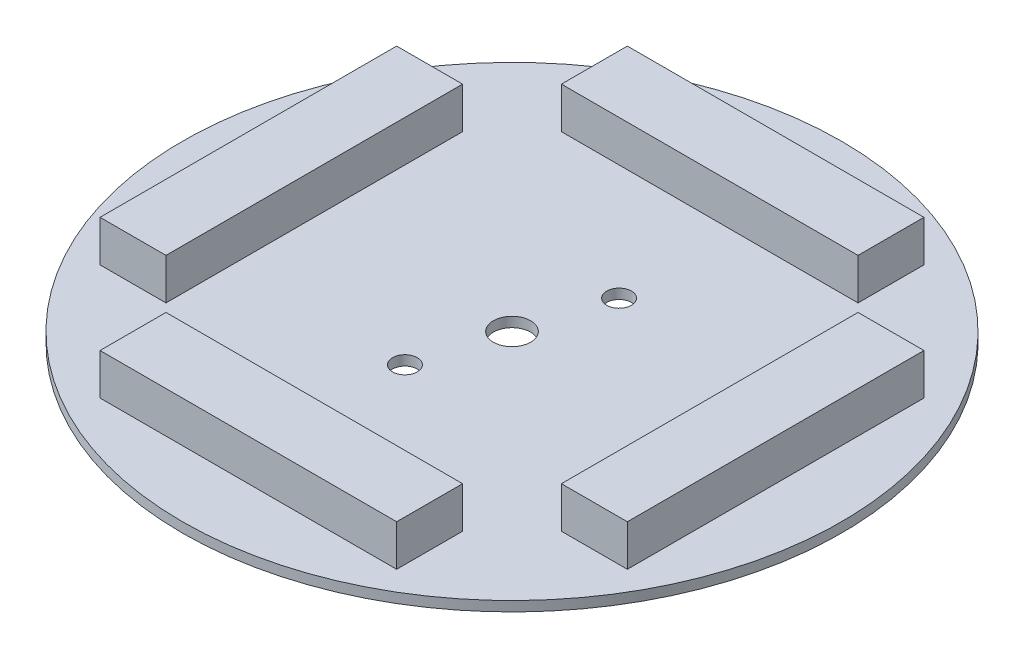
SolidWorks part; units mm, degrees
material "A-Glass Fiber"
ref_plane "Front Plane" through (0, 0, 0) normal (0, 0, 1) x (1, 0, 0)
ref_plane "Top Plane" through (0, 0, 0) normal (0, 1, 0) x (1, 0, 0)
ref_plane "Right Plane" through (0, 0, 0) normal (1, 0, 0) x (0, 0, -1)
sketch "Sketch1" plane through (0, 0, 0) normal (0, 1, 0) x (1, 0, 0)
  line L0 (1.5, 5) -> (0, 0) construction
  line L1 (0, 20) -> (0, -20) construction
  line L2 (0, 0) -> (-1.5, -5) construction
  circle A0 centre (0, 0) radius 20
  circle A1 centre (0, 0) radius 1.1303
  circle A2 centre (1.5, 5) radius 0.75
  circle A3 centre (-1.5, -5) radius 0.75
  dimension "D1" = 40
  dimension "D5" = 2.2606
  dimension "D6" = 1.5
  dimension "D7" = 1.5
  dimension "D2" = 1.5
  dimension "D3" = 5
  dimension "D4" = 5
extrude "PCB" add sketch "Sketch1" along normal blind 0.6 contours A0 | A3 | A1 | A2
sketch "Sketch2" plane through (0, 0.6, 0) normal (0, 1, 0) x (1, 0, 0)
  line L0 (0, 20) -> (0, 0) construction
  line L1 (-9, 16) -> (9, 16)
  line L2 (-9, 16) -> (-9, 12)
  line L3 (-9, 12) -> (9, 12)
  line L4 (9, 16) -> (9, 12)
  circle A0 centre (0, 0) radius 20 construction
  point P9 (0, 16)
  dimension "D1" = 4
  dimension "D2" = 18
  dimension "D3" = 16
extrude "Hirose Connector Stack" add sketch "Sketch2" along normal blind 2.5 contours L1 L4 L3 L2
pattern_circular "CirPattern1" count 4 over 360 about axis through (0, 0.6, 0) along (0, 1, 0) of "Hirose Connector Stack"
